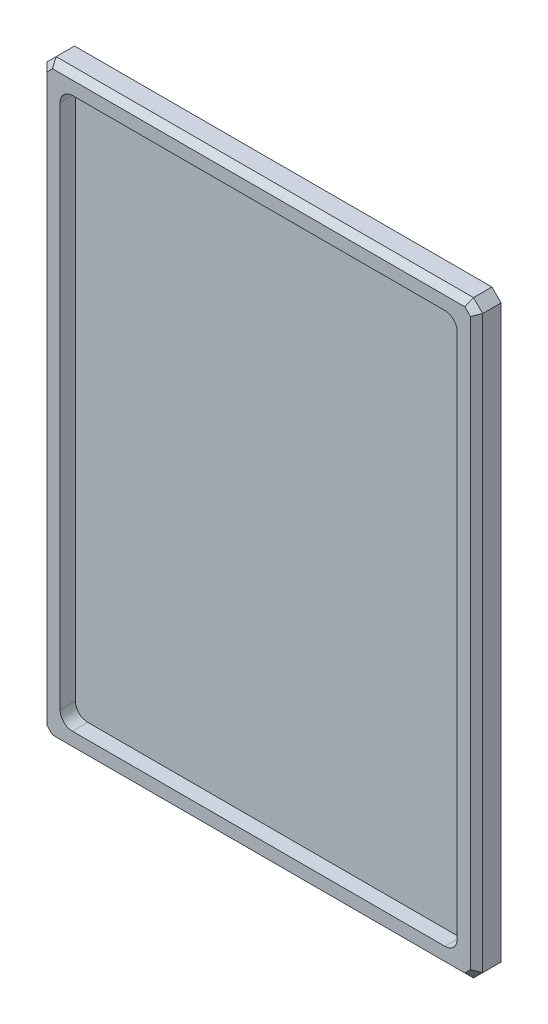
SolidWorks part; units mm, degrees
material "AISI 304"
ref_plane "Front Plane" through (0, 0, 0) normal (0, 0, 1) x (1, 0, 0)
ref_plane "Top Plane" through (0, 0, 0) normal (0, 1, 0) x (1, 0, 0)
ref_plane "Right Plane" through (0, 0, 0) normal (1, 0, 0) x (0, 0, -1)
sketch "Sketch1" plane through (0, 0, 0) normal (0, 0, 1) x (1, 0, 0)
  line L1 (112.7125, -152.4) -> (-112.7125, -152.4)
  line L2 (112.7125, -152.4) -> (112.7125, 152.4)
  line L3 (112.7125, 152.4) -> (-112.7125, 152.4)
  line L4 (-112.7125, -152.4) -> (-112.7125, 152.4)
  line L5 (112.7125, -152.4) -> (-112.7125, 152.4) construction
  line L6 (112.7125, 152.4) -> (-112.7125, -152.4) construction
  point P0 (0, 0)
  dimension "D1" = 304.8
  dimension "D2" = 225.425
extrude "Boss-Extrude1" add sketch "Sketch1" along normal blind 12.7
sketch "Sketch2" plane through (0, 0, 12.7) normal (0, 0, 1) x (1, 0, 0)
  line L0 (-112.7125, 152.4) -> (-112.7125, -152.4) construction
  line L1 (96.3625, -142.4) -> (-96.3625, -142.4)
  line L2 (102.7125, -136.05) -> (102.7125, 136.05)
  line L3 (96.3625, 142.4) -> (-96.3625, 142.4)
  line L4 (-102.7125, -136.05) -> (-102.7125, 136.05)
  line L5 (102.7125, -142.4) -> (-102.7125, 142.4) construction
  line L6 (102.7125, 142.4) -> (-102.7125, -142.4) construction
  line L7 (112.7125, 152.4) -> (-112.7125, 152.4) construction
  arc A0 (-96.3625, -142.4) -> (-102.7125, -136.05) centre (-96.3625, -136.05) cw
  arc A1 (96.3625, -142.4) -> (102.7125, -136.05) centre (96.3625, -136.05) ccw
  arc A2 (102.7125, 136.05) -> (96.3625, 142.4) centre (96.3625, 136.05) ccw
  arc A3 (-96.3625, 142.4) -> (-102.7125, 136.05) centre (-96.3625, 136.05) ccw
  point P0 (0, 0)
  dimension "D3" = 6.35
  dimension "D1" = 10
  dimension "D2" = 10
extrude "Cut-Extrude1" cut sketch "Sketch2" against normal blind 7.9375
chamfer "Chamfer2" distance 4.7625 angle 45 4 edges at (-112.7125, -152.4, 6.35) (-112.7125, 152.4, 6.35) (112.7125, -152.4, 6.35) (112.7125, 152.4, 6.35)
chamfer "Chamfer1" distance 3.175 angle 45 8 edges at (0, -152.4, 12.7) (-112.7125, 0, 12.7) (112.7125, 0, 12.7) (0, 152.4, 12.7) (-110.3313, -150.0188, 12.7) (110.3313, -150.0188, 12.7) (-110.3312, 150.0187, 12.7) (110.3313, 150.0187, 12.7)
